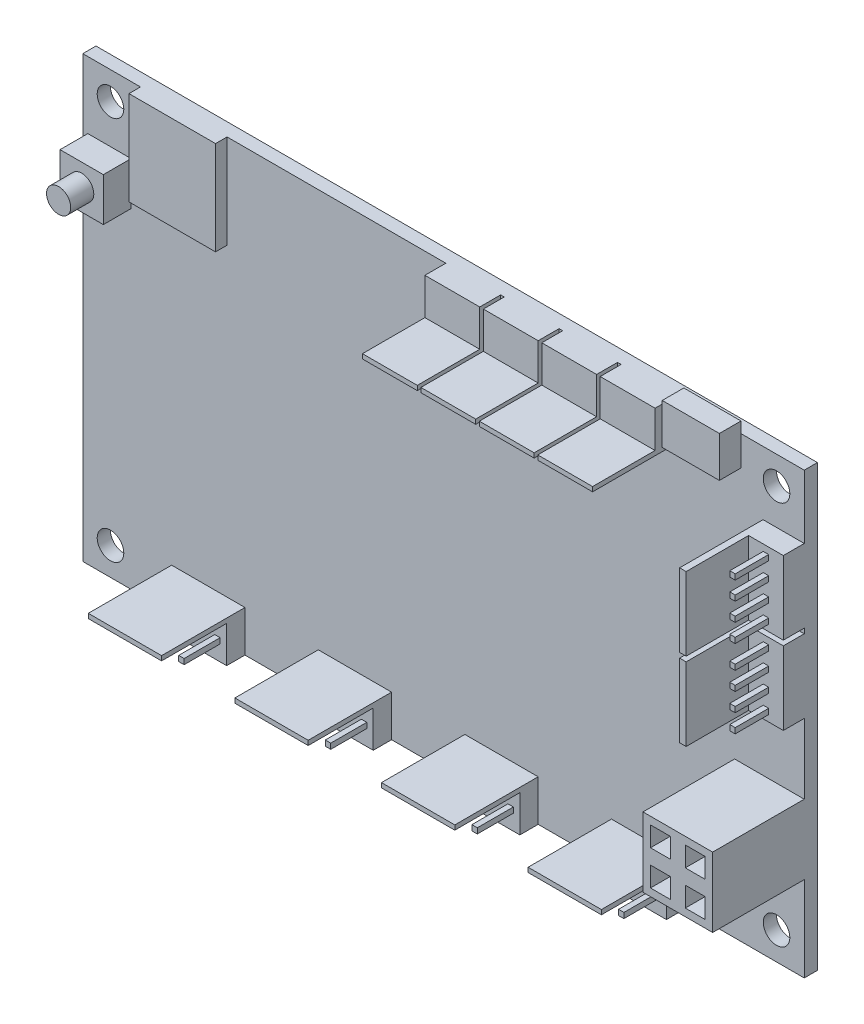
SolidWorks part; units mm, degrees
ref_plane "Front Plane" through (0, 0, 0) normal (0, 0, 1) x (1, 0, 0)
ref_plane "Top Plane" through (0, 0, 0) normal (0, 1, 0) x (1, 0, 0)
ref_plane "Right Plane" through (0, 0, 0) normal (1, 0, 0) x (0, 0, -1)
sketch "Sketch1" plane through (0, 0, 0) normal (0, 0, 1) x (1, 0, 0)
  line L1 (0, 0) -> (100, 0)
  line L2 (0, 0) -> (0, 60.96)
  line L3 (0, 60.96) -> (100, 60.96)
  line L4 (100, 0) -> (100, 60.96)
  dimension "D1" = 60.96
  dimension "D2" = 100
extrude "Boss-Extrude1" add sketch "Sketch1" along normal blind 1.8288
sketch "Sketch2" plane through (0, 0, 1.8288) normal (0, 0, 1) x (1, 0, 0)
  line L0 (0, 0) -> (100, 0) construction
  line L1 (12.319, 5.715) -> (22.479, 5.715)
  line L2 (12.319, 5.715) -> (12.319, 0)
  line L3 (12.319, 0) -> (22.479, 0)
  line L4 (22.479, 5.715) -> (22.479, 0)
  line L5 (12.319, 5.715) -> (22.479, 0) construction
  line L6 (12.319, 0) -> (22.479, 5.715) construction
  line L7 (0, 60.96) -> (0, 0) construction
  line L8 (32.639, 5.715) -> (42.799, 0) construction
  line L9 (32.639, 0) -> (42.799, 5.715) construction
  line L10 (32.639, 5.715) -> (42.799, 5.715)
  line L11 (42.799, 5.715) -> (42.799, 0)
  line L12 (32.639, 0) -> (42.799, 0)
  line L13 (32.639, 5.715) -> (32.639, 0)
  line L14 (52.959, 5.715) -> (63.119, 0) construction
  line L15 (52.959, 0) -> (63.119, 5.715) construction
  line L16 (52.959, 5.715) -> (63.119, 5.715)
  line L17 (63.119, 5.715) -> (63.119, 0)
  line L18 (52.959, 0) -> (63.119, 0)
  line L19 (52.959, 5.715) -> (52.959, 0)
  line L20 (73.279, 5.715) -> (83.439, 0) construction
  line L21 (73.279, 0) -> (83.439, 5.715) construction
  line L22 (73.279, 5.715) -> (83.439, 5.715)
  line L23 (83.439, 5.715) -> (83.439, 0)
  line L24 (73.279, 0) -> (83.439, 0)
  line L25 (73.279, 5.715) -> (73.279, 0)
  line L26 (12.319, 5.715) -> (32.639, 5.715) construction
  line L27 (100, 0) -> (100, 60.96) construction
  line L28 (100, 52.16) -> (94.285, 52.16)
  line L29 (100, 52.16) -> (100, 42)
  line L30 (100, 42) -> (94.285, 42)
  line L31 (94.285, 52.16) -> (94.285, 42)
  line L32 (100, 52.16) -> (94.285, 42) construction
  line L33 (100, 42) -> (94.285, 52.16) construction
  line L34 (100, 60.96) -> (0, 60.96) construction
  line L35 (100, 41.32) -> (94.285, 41.32)
  line L36 (100, 41.32) -> (100, 31.16)
  line L37 (100, 31.16) -> (94.285, 31.16)
  line L38 (94.285, 41.32) -> (94.285, 31.16)
  line L39 (100, 41.32) -> (94.285, 31.16) construction
  line L40 (100, 31.16) -> (94.285, 41.32) construction
  point P4 (17.399, 2.8575)
  point P27 (97.1425, 47.08)
  point P34 (97.1425, 36.24)
  dimension "D1" = 10.16
  dimension "D2" = 5.715
  dimension "D3" = 12.319
  dimension "D5" = 20.32
  dimension "D6" = 21
  dimension "D7" = 8.8
  dimension "D4" = 4
extrude "4 pin molex" add sketch "Sketch2" along normal blind 11.557
sketch "Sketch3" plane through (83.439, 0, 0) normal (1, 0, 0) x (0, 0, -1)
  line L0 (-13.3858, 5.715) -> (-1.8288, 5.715) construction
  line L1 (-13.3858, 0) -> (-4.3688, 0)
  line L2 (-13.3858, 0) -> (-13.3858, 5.08)
  line L3 (-13.3858, 5.08) -> (-4.3688, 5.08)
  line L4 (-4.3688, 0) -> (-4.3688, 5.08)
  line L5 (-13.3858, 0) -> (-4.3688, 5.08) construction
  line L6 (-13.3858, 5.08) -> (-4.3688, 0) construction
  line L7 (-1.8288, 0) -> (-1.8288, 31.16) construction
  point P4 (-8.8773, 2.54)
  dimension "D1" = 0.635
  dimension "D2" = 2.54
extrude "Cut-Extrude1" cut sketch "Sketch3" against normal through all
sketch "Sketch7" plane through (0, 31.16, 0) normal (0, -1, 0) x (-1, 0, 0)
  line L1 (-100, -13.3858) -> (-95.185, -13.3858)
  line L2 (-100, -13.3858) -> (-100, -4.7288)
  line L3 (-100, -4.7288) -> (-95.185, -4.7288)
  line L4 (-95.185, -13.3858) -> (-95.185, -4.7288)
  line L5 (-100, -13.3858) -> (-95.185, -4.7288) construction
  line L6 (-100, -4.7288) -> (-95.185, -13.3858) construction
  line L8 (-94.285, -13.3858) -> (-94.285, -1.8288) construction
  line L9 (-83.439, -1.8288) -> (-100, -1.8288) construction
  point P4 (-97.5925, -9.0573)
  dimension "D1" = 0.9
  dimension "D2" = 2.9
extrude "Cut-Extrude2" cut sketch "Sketch7" against normal blind 24.6
sketch "Sketch4" plane through (0, 0, 1.8288) normal (0, 0, 1) x (1, 0, 0)
  line L0 (100, 0) -> (100, 31.16) construction
  line L1 (100, 21.463) -> (90.348, 21.463)
  line L2 (100, 21.463) -> (100, 11.811)
  line L3 (100, 11.811) -> (90.348, 11.811)
  line L4 (90.348, 21.463) -> (90.348, 11.811)
  line L5 (100, 21.463) -> (90.348, 11.811) construction
  line L6 (100, 11.811) -> (90.348, 21.463) construction
  line L7 (83.439, 0) -> (100, 0) construction
  point P4 (95.174, 16.637)
  dimension "D1" = 9.652
  dimension "D2" = 9.652
  dimension "D3" = 11.811
extrude "Power Connector" add sketch "Sketch4" along normal blind 12.7
sketch "Sketch5" plane through (0, 0, 1.8288) normal (0, 0, 1) x (1, 0, 0)
  line L0 (100, 21.463) -> (100, 31.16) construction
  line L1 (83.3122, 56.8452) -> (91.237, 56.8452)
  line L2 (83.3122, 56.8452) -> (83.3122, 62.484)
  line L3 (83.3122, 62.484) -> (91.237, 62.484)
  line L4 (91.237, 56.8452) -> (91.237, 62.484)
  line L5 (83.3122, 56.8452) -> (91.237, 62.484) construction
  line L6 (83.3122, 62.484) -> (91.237, 56.8452) construction
  line L7 (100, 60.96) -> (0, 60.96) construction
  point P4 (87.2746, 59.6646)
  dimension "D1" = 7.9248
  dimension "D2" = 5.6388
  dimension "D3" = 8.763
  dimension "D4" = 1.524
extrude "MicroUSB" add sketch "Sketch5" along normal blind 3
sketch "Sketch6" plane through (0, 0, 1.8288) normal (0, 0, 1) x (1, 0, 0)
  line L0 (83.3122, 60.96) -> (0, 60.96) construction
  line L1 (8, 60.96) -> (20, 60.96)
  line L2 (8, 60.96) -> (8, 47.96)
  line L3 (8, 47.96) -> (20, 47.96)
  line L4 (20, 60.96) -> (20, 47.96)
  line L5 (8, 60.96) -> (20, 47.96) construction
  line L6 (8, 47.96) -> (20, 60.96) construction
  line L7 (0, 60.96) -> (0, 0) construction
  point P4 (14, 54.46)
  dimension "D1" = 12
  dimension "D2" = 13
  dimension "D3" = 8
extrude "MicroSD" add sketch "Sketch6" along normal blind 1.6
sketch "Sketch8" plane through (0, 0, 1.8288) normal (0, 0, 1) x (1, 0, 0)
  line L0 (0, 60.96) -> (0, 0) construction
  line L1 (0.7, 51.71) -> (6.7, 51.71)
  line L2 (0.7, 51.71) -> (0.7, 45.71)
  line L3 (0.7, 45.71) -> (6.7, 45.71)
  line L4 (6.7, 51.71) -> (6.7, 45.71)
  line L5 (0.7, 51.71) -> (6.7, 45.71) construction
  line L6 (0.7, 45.71) -> (6.7, 51.71) construction
  line L7 (8, 60.96) -> (0, 60.96) construction
  point P4 (3.7, 48.71)
  dimension "D1" = 6
  dimension "D2" = 6
  dimension "D3" = 6.7
  dimension "D4" = 9.25
extrude "Boss-Extrude6" add sketch "Sketch8" along normal blind 3.85
sketch "Sketch9" plane through (0, 0, 5.6788) normal (0, 0, 1) x (1, 0, 0)
  line L0 (0.7, 48.71) -> (3.7, 48.71) construction
  line L1 (0.7, 51.71) -> (0.7, 45.71) construction
  line L2 (3.7, 48.71) -> (3.7, 51.71) construction
  line L3 (6.7, 51.71) -> (0.7, 51.71) construction
  circle A0 centre (3.7, 48.71) radius 1.675
  dimension "D1" = 3.35
extrude "Boss-Extrude7" add sketch "Sketch9" along normal blind 3.2
sketch "Sketch10" plane through (0, 0, 1.8288) normal (0, 0, 1) x (1, 0, 0)
  line L0 (83.3122, 60.96) -> (20, 60.96) construction
  line L1 (82.22, 60.96) -> (74.62, 60.96)
  line L2 (82.22, 60.96) -> (82.22, 55.245)
  line L3 (82.22, 55.245) -> (74.62, 55.245)
  line L4 (74.62, 60.96) -> (74.62, 55.245)
  line L5 (82.22, 60.96) -> (74.62, 55.245) construction
  line L6 (82.22, 55.245) -> (74.62, 60.96) construction
  line L7 (100, 52.16) -> (100, 60.96) construction
  line L8 (74.12, 55.245) -> (66.52, 55.245)
  line L9 (66.52, 60.96) -> (66.52, 55.245)
  line L10 (74.12, 55.245) -> (66.52, 60.96) construction
  line L11 (74.12, 60.96) -> (66.52, 55.245) construction
  line L12 (74.12, 60.96) -> (66.52, 60.96)
  line L13 (74.12, 60.96) -> (74.12, 55.245)
  line L14 (66.02, 55.245) -> (58.42, 55.245)
  line L15 (58.42, 60.96) -> (58.42, 55.245)
  line L16 (66.02, 55.245) -> (58.42, 60.96) construction
  line L17 (66.02, 60.96) -> (58.42, 55.245) construction
  line L18 (66.02, 60.96) -> (58.42, 60.96)
  line L19 (66.02, 60.96) -> (66.02, 55.245)
  line L20 (57.92, 55.245) -> (50.32, 55.245)
  line L21 (50.32, 60.96) -> (50.32, 55.245)
  line L22 (57.92, 55.245) -> (50.32, 60.96) construction
  line L23 (57.92, 60.96) -> (50.32, 55.245) construction
  line L24 (57.92, 60.96) -> (50.32, 60.96)
  line L25 (57.92, 60.96) -> (57.92, 55.245)
  line L26 (82.22, 55.245) -> (74.12, 55.245) construction
  point P4 (78.42, 58.1025)
  dimension "D1" = 7.6
  dimension "D2" = 5.715
  dimension "D3" = 17.78
  dimension "D5" = 8.1
  dimension "D4" = 4
extrude "Boss-Extrude8" add sketch "Sketch10" along normal blind 11.557
sketch "Sketch11" plane through (82.22, 0, 0) normal (1, 0, 0) x (0, 0, -1)
  line L0 (-13.3858, 55.245) -> (-1.8288, 55.245) construction
  line L1 (-13.3858, 60.96) -> (-4.7288, 60.96)
  line L2 (-13.3858, 60.96) -> (-13.3858, 55.88)
  line L3 (-13.3858, 55.88) -> (-4.7288, 55.88)
  line L4 (-4.7288, 60.96) -> (-4.7288, 55.88)
  line L5 (-13.3858, 60.96) -> (-4.7288, 55.88) construction
  line L6 (-13.3858, 55.88) -> (-4.7288, 60.96) construction
  line L7 (-1.8288, 52.16) -> (-1.8288, 60.96) construction
  point P4 (-9.0573, 58.42)
  dimension "D1" = 0.635
  dimension "D2" = 2.9
extrude "Cut-Extrude3" cut sketch "Sketch11" against normal blind 36.449
sketch "Sketch13" plane through (0, 0, 1.8288) normal (0, 0, 1) x (1, 0, 0)
  line L0 (8, 60.96) -> (0, 60.96) construction
  line L1 (0, 60.96) -> (0, 0) construction
  line L2 (100, 0) -> (100, 11.811) construction
  line L3 (83.439, 0) -> (100, 0) construction
  circle A0 centre (3.8415, 57.1185) radius 1.8415
  circle A1 centre (3.8415, 3.8415) radius 1.8415
  circle A2 centre (96.1585, 3.8415) radius 1.8415
  circle A3 centre (96.1585, 57.1185) radius 1.8415
  dimension "D1" = 3.683
  dimension "D2" = 2
  dimension "D3" = 2
  dimension "D4" = 2
  dimension "D5" = 2
extrude "Cut-Extrude4" cut sketch "Sketch13" against normal blind 36.449
sketch "Sketch14" plane through (0, 0, 14.5288) normal (0, 0, 1) x (1, 0, 0)
  line L0 (96.212, 20.425) -> (98.962, 17.675) construction
  line L1 (90.348, 21.463) -> (100, 21.463)
  line L2 (90.348, 21.463) -> (90.348, 11.811)
  line L3 (90.348, 11.811) -> (100, 11.811)
  line L4 (100, 21.463) -> (100, 11.811)
  line L5 (95.174, 11.811) -> (95.174, 21.463) construction
  line L6 (90.348, 16.637) -> (100, 16.637) construction
  line L7 (92.761, 14.224) -> (97.587, 14.224) construction
  line L8 (92.761, 14.224) -> (92.761, 19.05) construction
  line L9 (92.761, 19.05) -> (97.587, 19.05) construction
  line L10 (97.587, 14.224) -> (97.587, 19.05) construction
  line L11 (92.761, 14.224) -> (97.587, 19.05) construction
  line L12 (92.761, 19.05) -> (97.587, 14.224) construction
  line L13 (91.386, 17.675) -> (94.136, 17.675)
  line L14 (91.386, 17.675) -> (91.386, 20.425)
  line L15 (91.386, 20.425) -> (94.136, 20.425)
  line L16 (94.136, 17.675) -> (94.136, 20.425)
  line L17 (91.386, 17.675) -> (94.136, 20.425) construction
  line L18 (91.386, 20.425) -> (94.136, 17.675) construction
  line L19 (96.212, 17.675) -> (98.962, 20.425) construction
  line L20 (96.212, 17.675) -> (98.962, 17.675)
  line L21 (96.212, 17.675) -> (96.212, 20.425)
  line L22 (96.212, 20.425) -> (98.962, 20.425)
  line L23 (98.962, 17.675) -> (98.962, 20.425)
  line L24 (96.212, 15.599) -> (98.962, 12.849) construction
  line L25 (96.212, 12.849) -> (98.962, 15.599) construction
  line L26 (96.212, 12.849) -> (98.962, 12.849)
  line L27 (96.212, 12.849) -> (96.212, 15.599)
  line L28 (96.212, 15.599) -> (98.962, 15.599)
  line L29 (98.962, 12.849) -> (98.962, 15.599)
  line L30 (91.386, 15.599) -> (94.136, 12.849) construction
  line L31 (91.386, 12.849) -> (94.136, 15.599) construction
  line L32 (91.386, 12.849) -> (94.136, 12.849)
  line L33 (91.386, 12.849) -> (91.386, 15.599)
  line L34 (91.386, 15.599) -> (94.136, 15.599)
  line L35 (94.136, 12.849) -> (94.136, 15.599)
  line L36 (91.386, 20.425) -> (96.212, 20.425) construction
  line L37 (91.386, 20.425) -> (91.386, 15.599) construction
  point P4 (95.174, 16.637)
  point P56 (95.174, 16.637)
  dimension "D1" = 4.826
  dimension "D2" = 2.75
  dimension "D5" = 90
  dimension "D6" = 4.826
  dimension "D7" = 4.826
  dimension "D3" = 2
  dimension "D4" = 2
extrude "Cut-Extrude5" cut sketch "Sketch14" against normal blind 5 contours L26 L29 L28 L27 | L32 L35 L34 L33 | L13 L16 L15 L14 | L20 L23 L22 L21 region at (92.761, 19.05, 14.5288) region at (97.587, 19.05, 14.5288) region at (97.587, 14.224, 14.5288) region at (92.761, 14.224, 14.5288)
sketch "Sketch15" plane through (0, 0, 4.3688) normal (0, 0, 1) x (1, 0, 0)
  line L0 (52.959, 0) -> (52.959, 5.08) construction
  line L1 (22.479, 0) -> (12.319, 0)
  line L2 (22.479, 0) -> (22.479, 5.08)
  line L3 (22.479, 5.08) -> (12.319, 5.08)
  line L4 (12.319, 0) -> (12.319, 5.08)
  line L5 (17.399, 5.08) -> (17.399, 0) construction
  line L6 (22.479, 2.54) -> (12.319, 2.54) construction
  line L7 (42.799, 0) -> (32.639, 0)
  line L8 (42.799, 0) -> (42.799, 5.08)
  line L9 (42.799, 5.08) -> (32.639, 5.08)
  line L10 (32.639, 0) -> (32.639, 5.08)
  line L11 (37.719, 5.08) -> (37.719, 0) construction
  line L12 (42.799, 2.54) -> (32.639, 2.54) construction
  line L13 (63.119, 0) -> (52.959, 0)
  line L14 (63.119, 0) -> (63.119, 5.08)
  line L15 (63.119, 5.08) -> (52.959, 5.08)
  line L16 (52.959, 0) -> (52.959, 5.08)
  line L17 (58.039, 5.08) -> (58.039, 0) construction
  line L18 (63.119, 2.54) -> (52.959, 2.54) construction
  line L19 (52.959, 5.715) -> (52.959, 0) construction
  line L20 (94.285, 31.16) -> (100, 31.16) construction
  line L21 (83.439, 0) -> (73.279, 0)
  line L22 (83.439, 0) -> (83.439, 5.08)
  line L23 (83.439, 5.08) -> (73.279, 5.08)
  line L24 (73.279, 0) -> (73.279, 5.08)
  line L25 (78.359, 5.08) -> (78.359, 0) construction
  line L26 (83.439, 2.54) -> (73.279, 2.54) construction
  line L27 (100, 41.32) -> (95.185, 41.32)
  line L28 (100, 41.32) -> (100, 31.16)
  line L29 (100, 31.16) -> (95.185, 31.16)
  line L30 (95.185, 41.32) -> (95.185, 31.16)
  line L31 (97.5925, 31.16) -> (97.5925, 41.32) construction
  line L32 (100, 36.24) -> (95.185, 36.24) construction
  line L33 (94.285, 31.16) -> (95.185, 31.16) construction
  line L34 (100, 41.32) -> (94.285, 41.32) construction
  line L35 (95.185, 42) -> (100, 42)
  line L36 (95.185, 42) -> (95.185, 52.16)
  line L37 (95.185, 52.16) -> (100, 52.16)
  line L38 (100, 42) -> (100, 52.16)
  line L39 (97.5925, 52.16) -> (97.5925, 42) construction
  line L40 (95.185, 47.08) -> (100, 47.08) construction
  point P9 (54.229, 2.54)
  point P56 (56.769, 2.54)
  point P61 (59.309, 2.54)
  point P66 (61.849, 2.54)
  point P88 (37.719, 2.54)
  point P93 (58.039, 2.54)
  point P104 (54.229, 2.54)
  point P105 (78.359, 2.54)
  point P183 (97.5925, 47.08)
  point P207 (97.5925, 36.24)
  line B0 (57.144, 2.165) -> (56.394, 2.165)
  line B1 (54.604, 2.165) -> (53.854, 2.165)
  line B2 (54.604, 2.165) -> (54.604, 2.915)
  line B3 (54.604, 2.915) -> (53.854, 2.915)
  line B4 (53.854, 2.165) -> (53.854, 2.915)
  line B5 (57.144, 2.165) -> (57.144, 2.915)
  line B6 (57.144, 2.915) -> (56.394, 2.915)
  line B7 (56.394, 2.165) -> (56.394, 2.915)
  line B8 (59.684, 2.165) -> (58.934, 2.165)
  line B9 (59.684, 2.165) -> (59.684, 2.915)
  line B10 (59.684, 2.915) -> (58.934, 2.915)
  line B11 (58.934, 2.165) -> (58.934, 2.915)
  line B12 (62.224, 2.165) -> (61.474, 2.165)
  line B13 (62.224, 2.165) -> (62.224, 2.915)
  line B14 (62.224, 2.915) -> (61.474, 2.915)
  line B15 (61.474, 2.165) -> (61.474, 2.915)
  line B16 (54.604, 2.165) -> (53.854, 2.915) construction
  line B17 (54.604, 2.915) -> (53.854, 2.165) construction
  line B18 (57.144, 2.165) -> (56.394, 2.915) construction
  line B19 (57.144, 2.915) -> (56.394, 2.165) construction
  line B20 (59.684, 2.165) -> (58.934, 2.915) construction
  line B21 (59.684, 2.915) -> (58.934, 2.165) construction
  line B22 (62.224, 2.165) -> (61.474, 2.915) construction
  line B23 (62.224, 2.915) -> (61.474, 2.165) construction
  line B24 (54.229, 2.54) -> (56.769, 2.54) construction
  line B25 (97.9675, 35.345) -> (97.9675, 34.595)
  line B26 (97.9675, 32.805) -> (97.9675, 32.055)
  line B27 (97.9675, 32.805) -> (97.2175, 32.805)
  line B28 (97.2175, 32.805) -> (97.2175, 32.055)
  line B29 (97.9675, 32.055) -> (97.2175, 32.055)
  line B30 (97.9675, 35.345) -> (97.2175, 35.345)
  line B31 (97.2175, 35.345) -> (97.2175, 34.595)
  line B32 (97.9675, 34.595) -> (97.2175, 34.595)
  line B33 (97.9675, 37.885) -> (97.9675, 37.135)
  line B34 (97.9675, 37.885) -> (97.2175, 37.885)
  line B35 (97.2175, 37.885) -> (97.2175, 37.135)
  line B36 (97.9675, 37.135) -> (97.2175, 37.135)
  line B37 (97.9675, 40.425) -> (97.9675, 39.675)
  line B38 (97.9675, 40.425) -> (97.2175, 40.425)
  line B39 (97.2175, 40.425) -> (97.2175, 39.675)
  line B40 (97.9675, 39.675) -> (97.2175, 39.675)
  line B41 (97.9675, 32.805) -> (97.2175, 32.055) construction
  line B42 (97.2175, 32.805) -> (97.9675, 32.055) construction
  line B43 (97.9675, 35.345) -> (97.2175, 34.595) construction
  line B44 (97.2175, 35.345) -> (97.9675, 34.595) construction
  line B45 (97.9675, 37.885) -> (97.2175, 37.135) construction
  line B46 (97.2175, 37.885) -> (97.9675, 37.135) construction
  line B47 (97.9675, 40.425) -> (97.2175, 39.675) construction
  line B48 (97.2175, 40.425) -> (97.9675, 39.675) construction
  line B49 (97.5925, 32.43) -> (97.5925, 34.97) construction
  line B50 (97.9675, 46.185) -> (97.9675, 45.435)
  line B51 (97.9675, 43.645) -> (97.9675, 42.895)
  line B52 (97.9675, 43.645) -> (97.2175, 43.645)
  line B53 (97.2175, 43.645) -> (97.2175, 42.895)
  line B54 (97.9675, 42.895) -> (97.2175, 42.895)
  line B55 (97.9675, 46.185) -> (97.2175, 46.185)
  line B56 (97.2175, 46.185) -> (97.2175, 45.435)
  line B57 (97.9675, 45.435) -> (97.2175, 45.435)
  line B58 (97.9675, 48.725) -> (97.9675, 47.975)
  line B59 (97.9675, 48.725) -> (97.2175, 48.725)
  line B60 (97.2175, 48.725) -> (97.2175, 47.975)
  line B61 (97.9675, 47.975) -> (97.2175, 47.975)
  line B62 (97.9675, 51.265) -> (97.9675, 50.515)
  line B63 (97.9675, 51.265) -> (97.2175, 51.265)
  line B64 (97.2175, 51.265) -> (97.2175, 50.515)
  line B65 (97.9675, 50.515) -> (97.2175, 50.515)
  line B66 (97.9675, 43.645) -> (97.2175, 42.895) construction
  line B67 (97.2175, 43.645) -> (97.9675, 42.895) construction
  line B68 (97.9675, 46.185) -> (97.2175, 45.435) construction
  line B69 (97.2175, 46.185) -> (97.9675, 45.435) construction
  line B70 (97.9675, 48.725) -> (97.2175, 47.975) construction
  line B71 (97.2175, 48.725) -> (97.9675, 47.975) construction
  line B72 (97.9675, 51.265) -> (97.2175, 50.515) construction
  line B73 (97.2175, 51.265) -> (97.9675, 50.515) construction
  line B74 (97.5925, 43.27) -> (97.5925, 45.81) construction
  line B75 (16.504, 2.165) -> (15.754, 2.165)
  line B76 (13.964, 2.165) -> (13.214, 2.165)
  line B77 (13.964, 2.165) -> (13.964, 2.915)
  line B78 (13.964, 2.915) -> (13.214, 2.915)
  line B79 (13.214, 2.165) -> (13.214, 2.915)
  line B80 (16.504, 2.165) -> (16.504, 2.915)
  line B81 (16.504, 2.915) -> (15.754, 2.915)
  line B82 (15.754, 2.165) -> (15.754, 2.915)
  line B83 (19.044, 2.165) -> (18.294, 2.165)
  line B84 (19.044, 2.165) -> (19.044, 2.915)
  line B85 (19.044, 2.915) -> (18.294, 2.915)
  line B86 (18.294, 2.165) -> (18.294, 2.915)
  line B87 (21.584, 2.165) -> (20.834, 2.165)
  line B88 (21.584, 2.165) -> (21.584, 2.915)
  line B89 (21.584, 2.915) -> (20.834, 2.915)
  line B90 (20.834, 2.165) -> (20.834, 2.915)
  line B91 (13.964, 2.165) -> (13.214, 2.915) construction
  line B92 (13.964, 2.915) -> (13.214, 2.165) construction
  line B93 (16.504, 2.165) -> (15.754, 2.915) construction
  line B94 (16.504, 2.915) -> (15.754, 2.165) construction
  line B95 (19.044, 2.165) -> (18.294, 2.915) construction
  line B96 (19.044, 2.915) -> (18.294, 2.165) construction
  line B97 (21.584, 2.165) -> (20.834, 2.915) construction
  line B98 (21.584, 2.915) -> (20.834, 2.165) construction
  line B99 (13.589, 2.54) -> (16.129, 2.54) construction
  line B100 (36.824, 2.165) -> (36.074, 2.165)
  line B101 (34.284, 2.165) -> (33.534, 2.165)
  line B102 (34.284, 2.165) -> (34.284, 2.915)
  line B103 (34.284, 2.915) -> (33.534, 2.915)
  line B104 (33.534, 2.165) -> (33.534, 2.915)
  line B105 (36.824, 2.165) -> (36.824, 2.915)
  line B106 (36.824, 2.915) -> (36.074, 2.915)
  line B107 (36.074, 2.165) -> (36.074, 2.915)
  line B108 (39.364, 2.165) -> (38.614, 2.165)
  line B109 (39.364, 2.165) -> (39.364, 2.915)
  line B110 (39.364, 2.915) -> (38.614, 2.915)
  line B111 (38.614, 2.165) -> (38.614, 2.915)
  line B112 (41.904, 2.165) -> (41.154, 2.165)
  line B113 (41.904, 2.165) -> (41.904, 2.915)
  line B114 (41.904, 2.915) -> (41.154, 2.915)
  line B115 (41.154, 2.165) -> (41.154, 2.915)
  line B116 (34.284, 2.165) -> (33.534, 2.915) construction
  line B117 (34.284, 2.915) -> (33.534, 2.165) construction
  line B118 (36.824, 2.165) -> (36.074, 2.915) construction
  line B119 (36.824, 2.915) -> (36.074, 2.165) construction
  line B120 (39.364, 2.165) -> (38.614, 2.915) construction
  line B121 (39.364, 2.915) -> (38.614, 2.165) construction
  line B122 (41.904, 2.165) -> (41.154, 2.915) construction
  line B123 (41.904, 2.915) -> (41.154, 2.165) construction
  line B124 (33.909, 2.54) -> (36.449, 2.54) construction
  line B125 (77.464, 2.165) -> (76.714, 2.165)
  line B126 (74.924, 2.165) -> (74.174, 2.165)
  line B127 (74.924, 2.165) -> (74.924, 2.915)
  line B128 (74.924, 2.915) -> (74.174, 2.915)
  line B129 (74.174, 2.165) -> (74.174, 2.915)
  line B130 (77.464, 2.165) -> (77.464, 2.915)
  line B131 (77.464, 2.915) -> (76.714, 2.915)
  line B132 (76.714, 2.165) -> (76.714, 2.915)
  line B133 (80.004, 2.165) -> (79.254, 2.165)
  line B134 (80.004, 2.165) -> (80.004, 2.915)
  line B135 (80.004, 2.915) -> (79.254, 2.915)
  line B136 (79.254, 2.165) -> (79.254, 2.915)
  line B137 (82.544, 2.165) -> (81.794, 2.165)
  line B138 (82.544, 2.165) -> (82.544, 2.915)
  line B139 (82.544, 2.915) -> (81.794, 2.915)
  line B140 (81.794, 2.165) -> (81.794, 2.915)
  line B141 (74.924, 2.165) -> (74.174, 2.915) construction
  line B142 (74.924, 2.915) -> (74.174, 2.165) construction
  line B143 (77.464, 2.165) -> (76.714, 2.915) construction
  line B144 (77.464, 2.915) -> (76.714, 2.165) construction
  line B145 (80.004, 2.165) -> (79.254, 2.915) construction
  line B146 (80.004, 2.915) -> (79.254, 2.165) construction
  line B147 (82.544, 2.165) -> (81.794, 2.915) construction
  line B148 (82.544, 2.915) -> (81.794, 2.165) construction
  line B149 (74.549, 2.54) -> (77.089, 2.54) construction
sketch_block_instance "Block1-1"
sketch_block "Block1"
sketch_block_instance "4 pin molex-1"
sketch_block "Block2"
sketch_block_instance "Block2-1"
sketch_block_instance "Block2-4"
sketch_block_instance "Block2-5"
sketch_block_instance "Block2-6"
extrude "Boss-Extrude9" add sketch "Sketch15" along normal blind 5 contours B79 B76 B77 B78 | B82 B75 B80 B81 | B86 B83 B84 B85 | B90 B87 B88 B89 | B104 B101 B102 B103 | B107 B100 B105 B106 | B111 B108 B109 B110 | B115 B112 B113 B114 | B4 B1 B2 B3 | B7 B0 B5 B6 | B11 B8 B9 B10 | B15 B12 B13 B14 | B132 B125 B130 B131 | B129 B126 B127 B128 | B136 B133 B134 B135 | B140 B137 B138 B139 | B29 B26 B27 B28 | B32 B25 B30 B31 | B36 B33 B34 B35 | B40 B37 B38 B39 | B54 B51 B52 B53 | B57 B50 B55 B56 | B61 B58 B59 B60 | B65 B62 B63 B64 region at (56.769, 2.54, 4.3688) region at (54.229, 2.54, 4.3688) region at (59.309, 2.54, 4.3688) region at (61.849, 2.54, 4.3688) region at (97.5925, 34.97, 4.3688) region at (97.5925, 32.43, 4.3688) region at (97.5925, 37.51, 4.3688) region at (97.5925, 40.05, 4.3688) region at (97.5925, 45.81, 4.3688) region at (97.5925, 43.27, 4.3688) region at (97.5925, 48.35, 4.3688) region at (97.5925, 50.89, 4.3688) region at (16.129, 2.54, 4.3688) region at (13.589, 2.54, 4.3688) region at (18.669, 2.54, 4.3688) region at (21.209, 2.54, 4.3688) region at (36.449, 2.54, 4.3688) region at (33.909, 2.54, 4.3688) region at (38.989, 2.54, 4.3688) region at (41.529, 2.54, 4.3688) region at (77.089, 2.54, 4.3688) region at (74.549, 2.54, 4.3688) region at (79.629, 2.54, 4.3688) region at (82.169, 2.54, 4.3688)
sketch "Sketch16" plane through (0, 62.484, 0) normal (0, 1, 0) x (1, 0, 0)
  line L0 (91.237, -4.8288) -> (91.237, -1.8288) construction
  line L1 (91.237, -4.8288) -> (83.3122, -4.8288)
  line L2 (91.237, -4.8288) -> (91.237, -1.8288)
  line L3 (91.237, -1.8288) -> (83.3122, -1.8288)
  line L4 (83.3122, -4.8288) -> (83.3122, -1.8288)
  line L5 (91.237, -4.8288) -> (83.3122, -1.8288) construction
  line L6 (91.237, -1.8288) -> (83.3122, -4.8288) construction
  line L7 (91.237, -4.8288) -> (83.3122, -4.8288) construction
  point P4 (87.2746, -3.3288)
